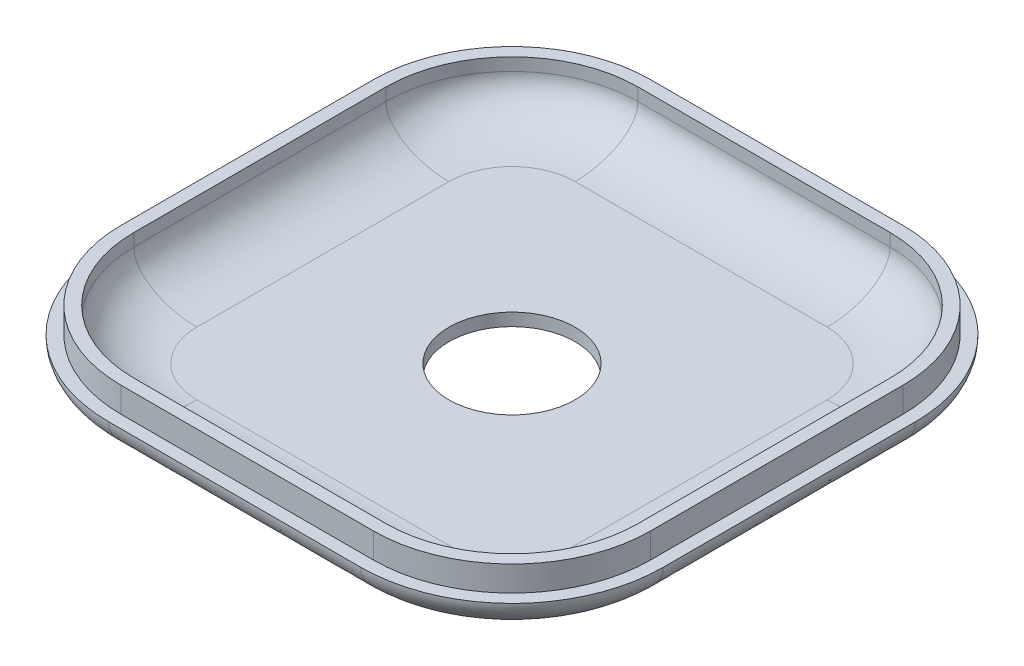
SolidWorks part; units mm, degrees
ref_plane "Front Plane" through (0, 0, 0) normal (0, 0, 1) x (1, 0, 0)
ref_plane "Top Plane" through (0, 0, 0) normal (0, 1, 0) x (1, 0, 0)
ref_plane "Right Plane" through (0, 0, 0) normal (1, 0, 0) x (0, 0, -1)
sketch "Sketch1" plane through (0, 0, 0) normal (0, 1, 0) x (1, 0, 0)
  line L0 (10, -1) -> (30, -1)
  line L1 (10, 0) -> (30, 0)
  line L2 (0, 10) -> (0, 30)
  line L3 (10, 40) -> (30, 40)
  line L4 (40, 10) -> (40, 30)
  line L5 (41, 10) -> (41, 30)
  line L6 (10, 41) -> (30, 41)
  line L7 (-1, 10) -> (-1, 30)
  line L8 (10, 42) -> (30, 42)
  line L9 (42, 10) -> (42, 30)
  line L10 (10, -2) -> (30, -2)
  line L11 (-2, 10) -> (-2, 30)
  arc A0 (30, 0) -> (40, 10) centre (30, 10) ccw
  arc A1 (0, 30) -> (10, 40) centre (10, 30) cw
  arc A2 (30, 40) -> (40, 30) centre (30, 30) cw
  arc A3 (10, 0) -> (0, 10) centre (10, 10) cw
  arc A4 (30, -1) -> (41, 10) centre (30, 10) ccw
  arc A5 (30, 41) -> (41, 30) centre (30, 30) cw
  arc A6 (-1, 30) -> (10, 41) centre (10, 30) cw
  arc A7 (10, -1) -> (-1, 10) centre (10, 10) cw
  arc A8 (0, 30) -> (10, 40) centre (10, 30) cw
  arc A9 (-2, 30) -> (10, 42) centre (10, 30) cw
  arc A10 (30, 42) -> (42, 30) centre (30, 30) cw
  arc A11 (30, -2) -> (42, 10) centre (30, 10) ccw
  arc A12 (10, -2) -> (-2, 10) centre (10, 10) cw
  circle A13 centre (20, 20) radius 5
  point P7 (40, 0)
  point P10 (0, 40)
  point P13 (40, 40)
  point P16 (0, 0)
  dimension "D3" = 10
  dimension "D1" = 40
  dimension "D2" = 40
  dimension "D4" = 1
  dimension "D5" = 1
  dimension "D6" = 2
extrude "Boss-Extrude2" add sketch "Sketch1" along normal blind 1 contours A3 L1 A0 L4 A2 L3 A1 L2 A13 region at (3.3289, 0, -3.3289)
extrude "Boss-Extrude3" add sketch "Sketch1<4>" along normal blind 5 contours A7 L0 A4 L5 A5 L6 A6 L7 L1 A3 L2 A1 L3 A2 L4 A0 region at (2.6418, 0, -2.6418)
sketch "Sketch1<4>" plane through (0, 0, 0) normal (0, 1, 0) x (1, 0, 0) same geometry as "Sketch1"
extrude "Boss-Extrude4" add sketch "Sketch1<5>" along normal blind 3 contours A12 L10 A11 L9 A10 L8 A9 L11 L0 A7 L7 A6 L6 A5 L5 A4 region at (20, 0, -41.3777)
sketch "Sketch1<5>" plane through (0, 0, 0) normal (0, 1, 0) x (1, 0, 0) same geometry as "Sketch1"
fillet "Fillet1" radius 5 8 edges at (40, 1, -20) (37.0711, 1, -2.9289) (37.0711, 1, -37.0711) (20, 1, 0) (20, 1, -40) (2.9289, 1, -2.9289) (2.9289, 1, -37.0711) (0, 1, -20) second distance 3 first distance on face at (20, 1, -15)
fillet "Fillet2" radius 5 8 edges at (20, 0, -42) (1.5147, 0, -38.4853) (38.4853, 0, -38.4853) (-2, 0, -20) (42, 0, -20) (1.5147, 0, -1.5147) (38.4853, 0, -1.5147) (20, 0, 2) second distance 3 first distance on face at (20, 0, -15)
